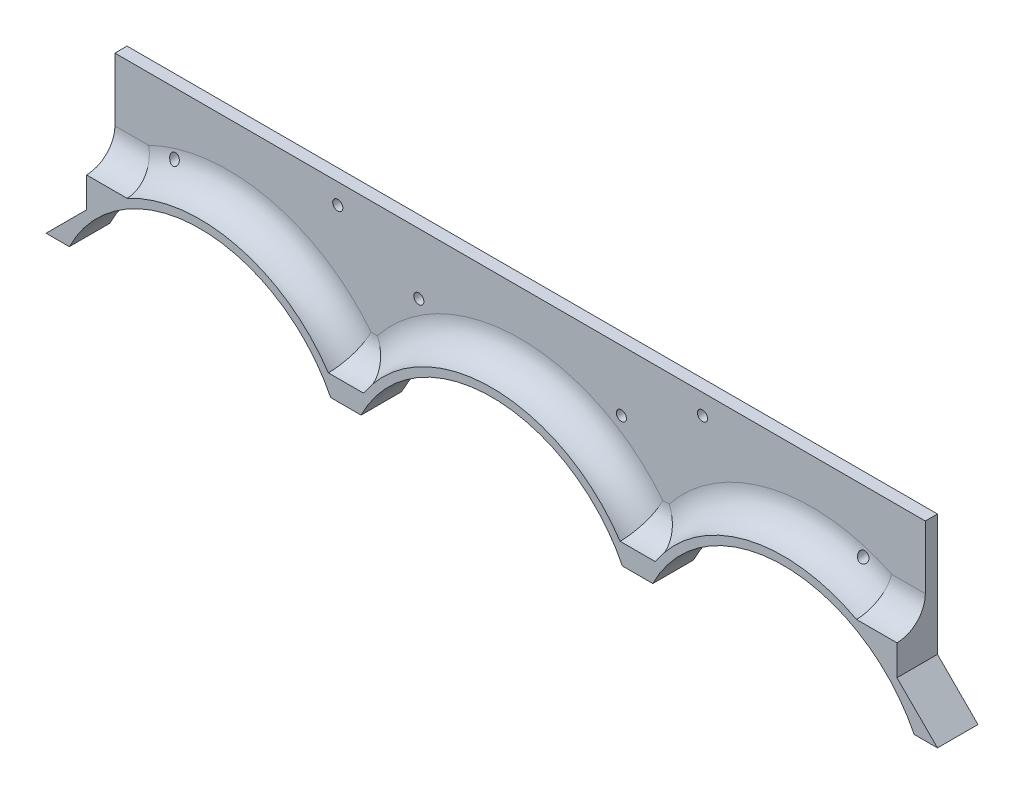
SolidWorks part; units mm, degrees
ref_plane "Front Plane" through (0, 0, 0) normal (0, 0, 1) x (1, 0, 0)
ref_plane "Top Plane" through (0, 0, 0) normal (0, 1, 0) x (1, 0, 0)
ref_plane "Right Plane" through (0, 0, 0) normal (1, 0, 0) x (0, 0, -1)
sketch "Sketch1" plane through (0, 0, 0) normal (0, 0, 1) x (1, 0, 0)
  line L0 (-100, 0) -> (100, 0)
  line L1 (-100, 0) -> (-100, -30)
  line L2 (110, -40) -> (104.2471, -40)
  line L3 (-110, -40) -> (-100, -30)
  line L4 (-110, -40) -> (-104.2471, -40)
  line L5 (-39.749, -40) -> (-32.249, -40)
  line L6 (32.249, -40) -> (39.749, -40)
  line L7 (100, 0) -> (100, -30)
  line L8 (100, -30) -> (110, -40)
  arc A0 (-39.749, -40) -> (-104.2471, -40) centre (-71.9981, -56) ccw
  arc A1 (32.249, -40) -> (-32.249, -40) centre (0, -56) ccw
  arc A2 (39.749, -40) -> (104.2471, -40) centre (71.9981, -56) cw
  point P3 (0, 0)
  point P13 (124.7947, -40.2798)
  point P15 (-109.7366, -20.9)
  dimension "D2" = 36
  dimension "D1" = 45
  dimension "D3" = 16
  dimension "D4" = 45
  dimension "D5" = 40
  dimension "D6" = 100
  dimension "D7" = 10
  dimension "D8" = 71.9981
  dimension "D9" = 7.5
extrude "Main" add sketch "Sketch1" along normal blind 10
sketch "Sketch2" plane through (0, 0, 10) normal (0, 0, 1) x (1, 0, 0)
  line L0 (-100, 0) -> (100, 0)
  line L1 (100, 0) -> (100, -22.5346)
  line L2 (100, -30) -> (100, 0) construction
  line L3 (100, -22.5346) -> (90, -22.5346)
  line L4 (40.3279, -35) -> (31.6702, -35)
  line L5 (32.249, -40) -> (39.749, -40) construction
  line L6 (-40.3279, -35) -> (-31.6702, -35)
  line L7 (-100, 0) -> (-100, -22.5346)
  line L8 (-100, 0) -> (-100, -30) construction
  line L9 (-100, -22.5346) -> (-90, -22.5346)
  arc A0 (90, -22.5346) -> (40.3279, -35) centre (71.9981, -56) ccw
  arc A2 (-40.3279, -35) -> (-90, -22.5346) centre (-71.9981, -56) ccw
  arc A3 (-39.749, -40) -> (-104.2471, -40) centre (-71.9981, -56) ccw construction
  arc A4 (-31.6702, -35) -> (31.6702, -35) centre (0, -56) cw
  point P17 (-92.9132, -16.7138)
  dimension "D2" = 38
  dimension "D3" = 10
  dimension "D1" = 5
extrude "BackCut" cut sketch "Sketch2" against normal blind 7
fillet "Fillet1" radius 7 7 edges at (-62.7487, -19.1429, 3) (-95, -22.5346, 3) (0, -18, 3) (95, -22.5346, 3) (62.7487, -19.1429, 3) (-35.999, -35, 3) (35.999, -35, 3)
sketch "Sketch3" plane through (0, 0, 3) normal (0, 0, 1) x (1, 0, 0)
  line L1 (100, 0) -> (-100, 0) construction
  circle A0 centre (-45, -5) radius 1.25
  circle A1 centre (45, -5) radius 1.25
  circle A2 centre (-25, -15) radius 1.25
  circle A3 centre (25, -15) radius 1.25
  circle A4 centre (-85, -15) radius 1.25
  circle A5 centre (85, -15) radius 1.25
  point P15 (113.4167, -16.9465)
  point P16 (0, 0)
  dimension "D1" = 2.5
  dimension "D11" = 2.5
  dimension "D2" = 45
  dimension "D3" = 5
  dimension "D4" = 45
  dimension "D5" = 25
  dimension "D6" = 15
  dimension "D7" = 25
  dimension "D8" = 15
  dimension "D9" = 85
  dimension "D10" = 85
extrude "FixHoles" cut sketch "Sketch3" against normal through all both and the other way through all
